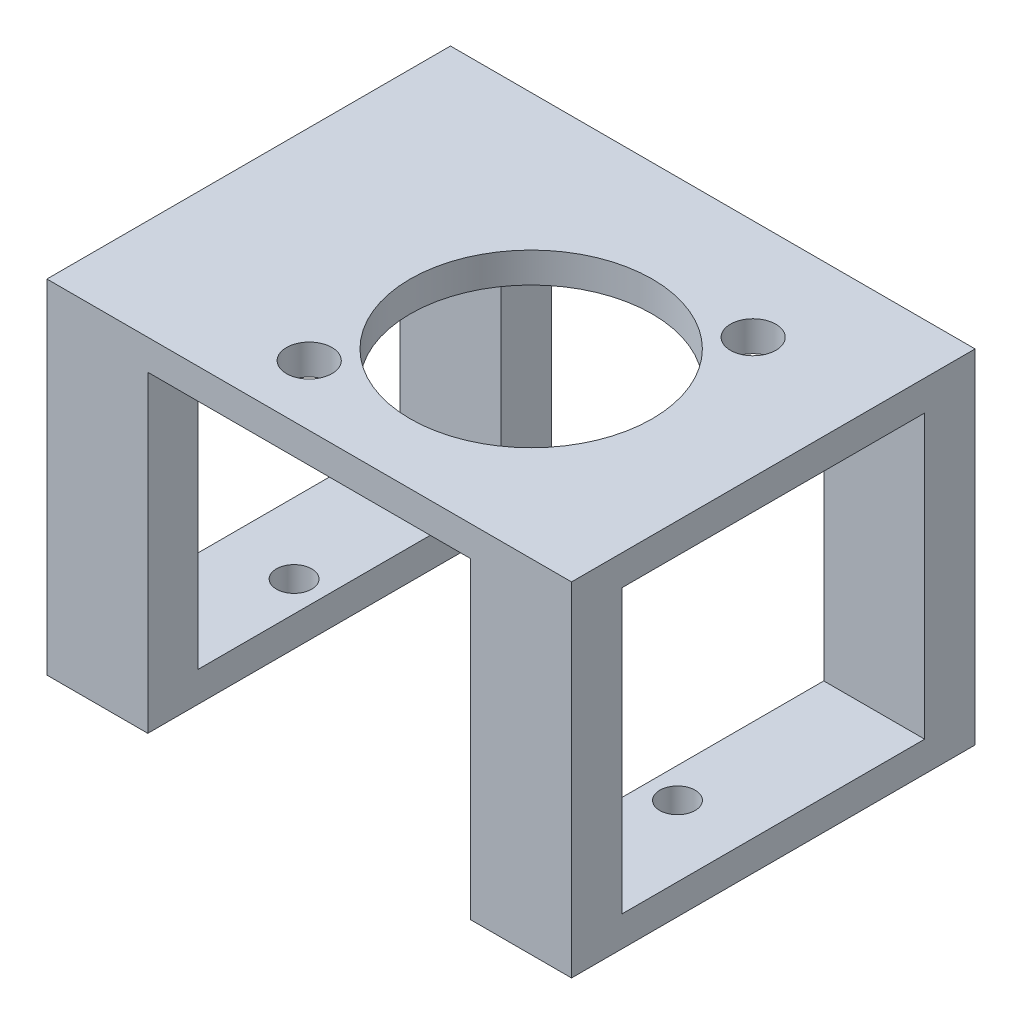
SolidWorks part; units mm, degrees
ref_plane "Front Plane" through (0, 0, 0) normal (0, 0, 1) x (1, 0, 0)
ref_plane "Top Plane" through (0, 0, 0) normal (0, 1, 0) x (1, 0, 0)
ref_plane "Right Plane" through (0, 0, 0) normal (1, 0, 0) x (0, 0, -1)
sketch "Sketch1" plane through (0, 0, 0) normal (0, 1, 0) x (1, 0, 0)
  line L0 (-16, 0) -> (16, 0)
  line L10 (-16, -12.5) -> (-26, -12.5)
  line L11 (-16, -12.5) -> (-16, 17.5)
  line L12 (-16, 17.5) -> (-26, 17.5)
  line L13 (16, -12.5) -> (26, -12.5)
  line L14 (16, -12.5) -> (16, 17.5)
  line L15 (-26, -12.5) -> (-26, 17.5)
  line L16 (-16, 17.5) -> (-26, 17.5)
  line L17 (16, 17.5) -> (26, 17.5)
  line L18 (26, -12.5) -> (26, 17.5)
  line L19 (16, 17.5) -> (26, 17.5)
  line L24 (16, 17.5) -> (16, 22.5)
  line L25 (16, 22.5) -> (26, 22.5)
  line L26 (26, 17.5) -> (26, 22.5)
  line L27 (-16, 17.5) -> (-16, 22.5)
  line L28 (-16, 22.5) -> (-26, 22.5)
  line L29 (-26, 17.5) -> (-26, 22.5)
  line L30 (-26, -12.5) -> (-16, -12.5)
  line L31 (-26, -12.5) -> (-26, -17.5)
  line L32 (-26, -17.5) -> (-16, -17.5)
  line L33 (-16, -12.5) -> (-16, -17.5)
  line L34 (16, -12.5) -> (26, -12.5)
  line L35 (16, -12.5) -> (16, -17.5)
  line L36 (16, -17.5) -> (26, -17.5)
  line L37 (26, -12.5) -> (26, -17.5)
  point P4 (0, 0)
  point P7 (16, 0)
  dimension "D1" = 5
  dimension "D2" = 10
  dimension "D3" = 5
  dimension "D4" = 10
  dimension "D5" = 30
  dimension "D6" = 30
  dimension "D7" = 32
  dimension "D8" = 12.5
  dimension "D9" = 12.5
  dimension "D10" = 16
  dimension "D11" = 16
  dimension "D12" = 5
  dimension "0.5" = 5
extrude "Boss-Extrude1" add sketch "Sketch1" along normal blind 3 contours L12 | L14 | L13 L18 L17 L14 | L33 L10 L31 L32 | L37 L13 L35 L36 region at (21, 0, -2.5) region at (-21, 0, -2.5) region at (-21, 0, 15) region at (21, 0, 15)
extrude "Boss-Extrude2" add sketch "Sketch1<3>" along normal blind 31 contours L29 L12 L27 L28 | L17 L26 L25 L24 region at (-21, 0, -20) region at (21, 0, -20)
sketch "Sketch1<3>" plane through (0, 0, 0) normal (0, 1, 0) x (1, 0, 0) same geometry as "Sketch1"
sketch "Sketch7" plane through (0, 31, 0) normal (0, 1, 0) x (1, 0, 0)
  line L1 (-26, 22.5) -> (26, 22.5)
  line L2 (-26, 22.5) -> (-26, -17.5)
  line L3 (-26, -17.5) -> (26, -17.5)
  line L4 (26, 22.5) -> (26, -17.5)
  dimension "D1" = 52
  dimension "D2" = 40
extrude "Boss-Extrude3" add sketch "Sketch7" along normal blind 3
sketch "Sketch8" plane through (0, 34, 0) normal (0, 1, 0) x (1, 0, 0)
  circle A0 centre (4, 0.5) radius 12
  circle A1 centre (-6, -11.5) radius 2.25
  circle A2 centre (14, 12.5) radius 2.25
  dimension "D7" = 4.5
  dimension "D8" = 4.5
  dimension "D9" = 24
  dimension "D1" = 22
  dimension "D2" = 4
  dimension "D3" = 10
  dimension "D4" = 10
  dimension "D5" = 12
  dimension "D6" = 12
extrude "Cut-Extrude4" cut sketch "Sketch8" against normal up to next (3 mm away)
sketch "Sketch10" plane through (0, 3, 0) normal (0, 1, 0) x (1, 0, 0)
  circle A0 centre (-19, 0) radius 1.75
  circle A1 centre (19, 0) radius 1.75
  dimension "D4" = 3.5
  dimension "0.6" = 3.5
  dimension "D1" = 17.5
  dimension "D2" = 7
  dimension "D3" = 3
  dimension "D5" = 17.5
extrude "Cut-Extrude5" cut sketch "Sketch10" against normal up to next (3 mm away)
sketch "Sketch11" plane through (0, 3, 0) normal (0, 1, 0) x (1, 0, 0)
  line L0 (-26, -17.5) -> (-26, 17.5) construction
  line L1 (-16, -17.5) -> (-26, -17.5)
  line L2 (-16, -17.5) -> (-16, -12.5)
  line L3 (-16, -12.5) -> (-26, -12.5)
  line L4 (-26, -17.5) -> (-26, -12.5)
  line L5 (26, -17.5) -> (26, 17.5) construction
  line L6 (16, -17.5) -> (26, -17.5)
  line L7 (16, -17.5) -> (16, -12.5)
  line L8 (16, -12.5) -> (26, -12.5)
  line L9 (26, -17.5) -> (26, -12.5)
  dimension "D1" = 5
  dimension "D2" = 5
extrude "Boss-Extrude4" add sketch "Sketch11" along normal up to next
